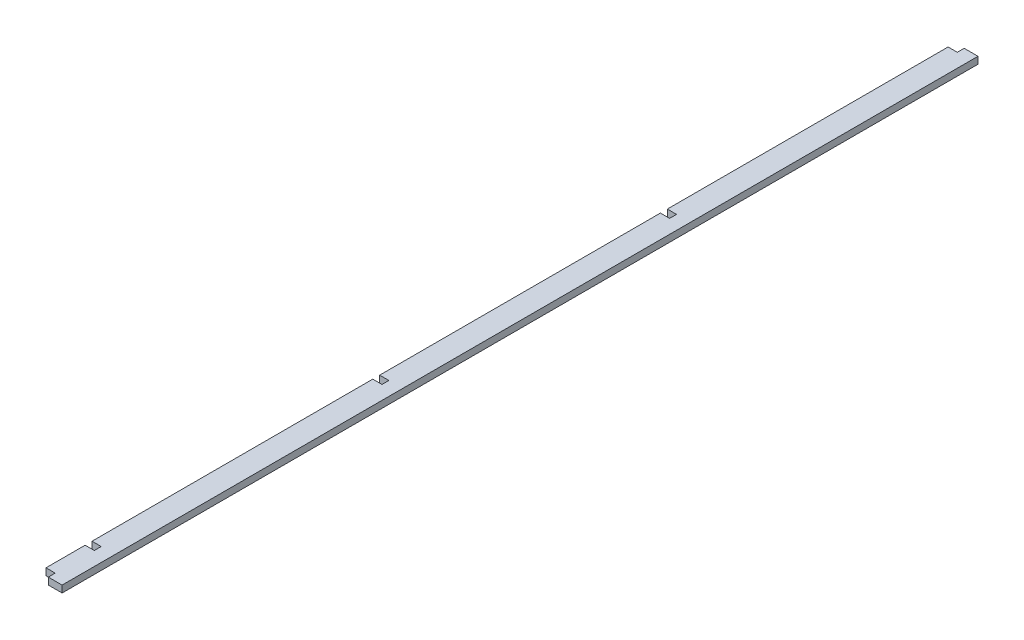
SolidWorks part; units mm, degrees
material "轻木"
ref_plane "前视基准面" through (0, 0, 0) normal (0, 0, 1) x (1, 0, 0)
ref_plane "上视基准面" through (0, 0, 0) normal (0, 1, 0) x (1, 0, 0)
ref_plane "右视基准面" through (0, 0, 0) normal (1, 0, 0) x (0, 0, -1)
other "Configuration Table"
sketch "草图1" plane through (0, 0, 1160.01) normal (0, 0, 1) x (1, 0, 0)
  line L1 (130.7876, -3.3897) -> (120.7876, -3.3897)
  line L2 (130.7876, -3.3897) -> (130.7876, -6.3897)
  line L3 (130.7876, -6.3897) -> (120.7876, -6.3897)
  line L4 (120.7876, -3.3897) -> (120.7876, -6.3897)
  dimension "D1" = 3
  dimension "D2" = 10
extrude "凸台-拉伸1" add sketch "草图1" against normal blind 400
sketch "草图2" plane through (0, -3.3897, 0) normal (0, 1, 0) x (1, 0, 0)
  line L0 (120.7876, -760.01) -> (120.7876, -1160.01) construction
  line L1 (120.7876, -762.01) -> (124.7876, -762.01)
  line L2 (120.7876, -762.01) -> (120.7876, -765.01)
  line L3 (120.7876, -765.01) -> (124.7876, -765.01)
  line L4 (124.7876, -762.01) -> (124.7876, -765.01)
  line L9 (130.7876, -762.01) -> (-44.1255, -762.01) construction
  line L10 (120.7876, -887.01) -> (124.7876, -887.01)
  line L11 (120.7876, -887.01) -> (120.7876, -890.01)
  line L12 (120.7876, -890.01) -> (124.7876, -890.01)
  line L13 (124.7876, -887.01) -> (124.7876, -890.01)
  line L22 (120.7876, -762.01) -> (120.7876, -887.01) construction
  line L24 (120.7876, -1160.01) -> (124.7876, -1160.01)
  line L25 (120.7876, -1160.01) -> (120.7876, -1157.01)
  line L26 (120.7876, -1157.01) -> (124.7876, -1157.01)
  line L27 (124.7876, -1160.01) -> (124.7876, -1157.01)
  line L30 (130.7876, -1012.01) -> (-44.1255, -1012.01) construction
  line L31 (124.7876, -1015.01) -> (120.7876, -1015.01)
  line L32 (124.7876, -1015.01) -> (124.7876, -1012.01)
  line L33 (124.7876, -1012.01) -> (120.7876, -1012.01)
  line L34 (120.7876, -1015.01) -> (120.7876, -1012.01)
  line L35 (124.7876, -1140.01) -> (120.7876, -1140.01)
  line L36 (124.7876, -1140.01) -> (124.7876, -1137.01)
  line L37 (124.7876, -1137.01) -> (120.7876, -1137.01)
  line L38 (120.7876, -1140.01) -> (120.7876, -1137.01)
  line L39 (124.7876, -1015.01) -> (124.7876, -1140.01) construction
  dimension "D2" = 125
  dimension "D4" = 125
  dimension "D1" = 2
  dimension "D3" = 2
extrude "切除-拉伸1" cut sketch "草图2" against normal through all
sketch "草图3" plane through (0, -3.3897, 0) normal (0, 1, 0) x (1, 0, 0)
  line L1 (130.7876, -760.01) -> (120.7876, -760.01)
  line L2 (130.7876, -760.01) -> (130.7876, -762.01)
  line L3 (130.7876, -762.01) -> (120.7876, -762.01)
  line L4 (120.7876, -760.01) -> (120.7876, -762.01)
extrude "切除-拉伸2" cut sketch "草图3" against normal through all
